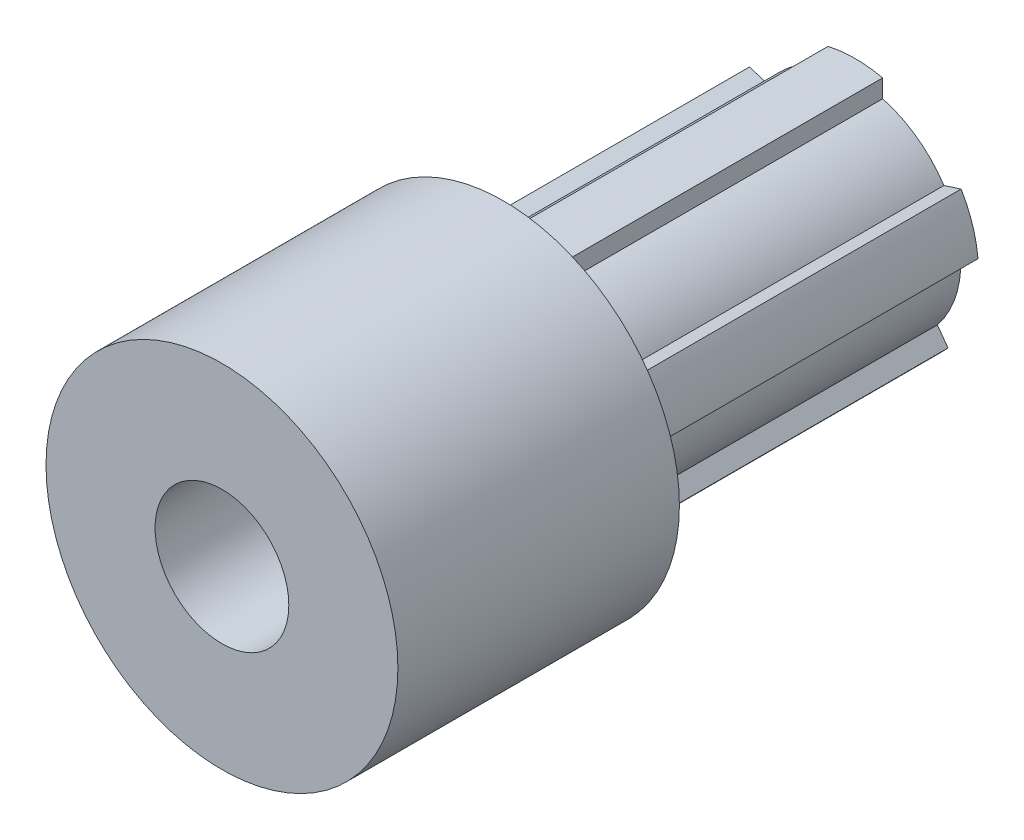
SolidWorks part; units mm, degrees
note: The reader was unsure of these and kept them because the rebuilt part matched: shared geometry of "Sketch2<3>".
ref_plane "Front Plane" through (0, 0, 0) normal (0, 0, 1) x (1, 0, 0)
ref_plane "Top Plane" through (0, 0, 0) normal (0, 1, 0) x (1, 0, 0)
ref_plane "Right Plane" through (0, 0, 0) normal (1, 0, 0) x (0, 0, -1)
sketch "Sketch1" plane through (0, 0, 0) normal (0, 0, 1) x (1, 0, 0)
  circle A0 centre (0, 0) radius 25
extrude "Boss-Extrude1" add sketch "Sketch1" along normal blind 90
sketch "Sketch2" plane through (0, 0, 0) normal (0, 0, -1) x (-1, 0, 0)
  line L0 (0, 15) -> (0, 10.569) construction
  line L5 (12.5813, 8.1676) -> (15.0303, 8.9633)
  line L6 (3.88, 14.4895) -> (3.88, 17.0645)
  line L7 (-3.88, 14.4895) -> (-3.88, 17.0645)
  line L8 (14.9793, 0.7874) -> (17.4282, 1.5831)
  line L9 (11.6557, -9.4416) -> (13.1692, -11.5248)
  line L10 (5.3777, -14.0029) -> (6.8912, -16.086)
  line L11 (-5.3777, -14.0029) -> (-6.8912, -16.086)
  line L12 (-11.6557, -9.4416) -> (-13.1692, -11.5248)
  line L13 (-14.9793, 0.7874) -> (-17.4282, 1.5831)
  line L14 (-12.5813, 8.1676) -> (-15.0303, 8.9633)
  arc A0 (3.88, 14.4895) -> (-3.88, 14.4895) centre (0, 0) ccw
  arc A2 (0, 15) -> (3.88, 14.4895) centre (0, 0) cw
  arc A3 (0, 15) -> (-3.88, 14.4895) centre (0, 0) ccw
  circle A4 centre (0, 0) radius 25
  arc A5 (3.88, 17.0645) -> (-3.88, 17.0645) centre (0, 0) ccw
  arc A6 (17.4282, 1.5831) -> (15.0303, 8.9633) centre (0, 0) ccw
  arc A7 (14.9793, 0.7874) -> (12.5813, 8.1676) centre (0, 0) ccw
  arc A8 (6.8912, -16.086) -> (13.1692, -11.5248) centre (0, 0) ccw
  arc A9 (5.3777, -14.0029) -> (11.6557, -9.4416) centre (0, 0) ccw
  arc A10 (-13.1692, -11.5248) -> (-6.8912, -16.086) centre (0, 0) ccw
  arc A11 (-11.6557, -9.4416) -> (-5.3777, -14.0029) centre (0, 0) ccw
  arc A12 (-15.0303, 8.9633) -> (-17.4282, 1.5831) centre (0, 0) ccw
  arc A13 (-12.5813, 8.1676) -> (-14.9793, 0.7874) centre (0, 0) ccw
  circle A14 centre (0, 0) radius 15
  circle A15 centre (0, 0) radius 17.5
  dimension "D1" = 30
  dimension "D2" = 3.88
  dimension "D3" = 5
  dimension "D5" = 3.88
extrude "Cut-Extrude2" cut sketch "Sketch2" against normal blind 50
extrude "Cut-Extrude4" cut sketch "Sketch2<3>" against normal blind 50 contours L7 A15 L14 A14 | L5 A15 L6 A14 | L9 A15 L8 A14 | L11 A15 L10 A14 | L13 A15 L12 A14
sketch "Sketch2<3>" plane through (0, 0, 0) normal (0, 0, -1) x (-1, 0, 0) same geometry as "Sketch2"
sketch "Sketch3" plane through (0, 0, 90) normal (0, 0, 1) x (1, 0, 0)
  circle A0 centre (0, 0) radius 9.5
extrude "Cut-Extrude5" cut sketch "Sketch3" against normal blind 29.2
ref_plane "Plane1" through (0, 6.68, 0) normal (0, 1, 0) x (1, 0, 0)
sketch "Sketch5" plane through (0, 6.68, 0) normal (0, 1, 0) x (1, 0, 0)
  line L0 (0, -90) -> (0, -85.2) construction
  line L1 (-25, -90) -> (25, -90) construction
  line L2 (0, -85.2) -> (0, -82.2) construction
  line L3 (0, -82.2) -> (0, -57.2) construction
  line L4 (-3, -82.2) -> (-3, -57.2)
  line L5 (3, -82.2) -> (3, -57.2)
  arc A0 (-3, -82.2) -> (3, -82.2) centre (0, -82.2) ccw
  arc A1 (3, -57.2) -> (-3, -57.2) centre (0, -57.2) ccw
  point P5 (0, -69.7)
  dimension "D1" = 3
  dimension "D2" = 6
  dimension "D3" = 25
extrude "Cut-Extrude6" cut sketch "Sketch5" along normal blind 4
